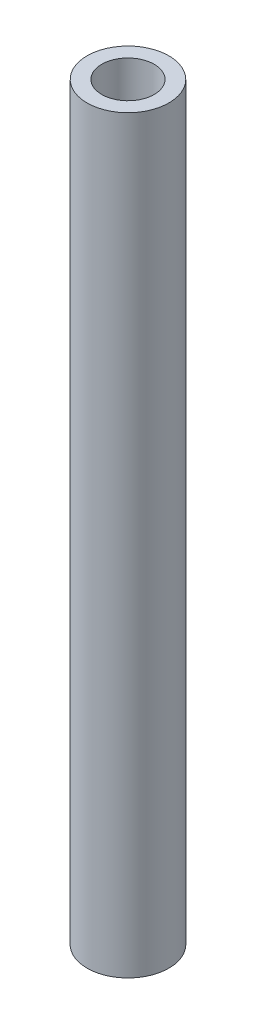
SolidWorks part; units mm, degrees
material "1.5714 (16NiCr4)"
ref_plane "Plan de face" through (0, 0, 0) normal (0, 0, 1) x (1, 0, 0)
ref_plane "Plan de dessus" through (0, 0, 0) normal (0, 1, 0) x (1, 0, 0)
ref_plane "Plan de droite" through (0, 0, 0) normal (1, 0, 0) x (0, 0, -1)
sketch "Esquisse1" plane through (0, 0, 0) normal (0, 1, 0) x (1, 0, 0)
  circle A0 centre (-34.3904, -12.561) radius 3.85
  circle A1 centre (-34.3904, -12.561) radius 6
  dimension "D1" = 12
  dimension "D2" = 7.7
extrude "Boss.-Extru.1" add sketch "Esquisse1" along normal blind 110 contours A1
extrude "Enlèv. mat.-Extru.1" cut sketch "Esquisse1<3>" along normal blind 110 contours A0
sketch "Esquisse1<3>" plane through (0, 0, 0) normal (0, 1, 0) x (1, 0, 0) same geometry as "Esquisse1"
